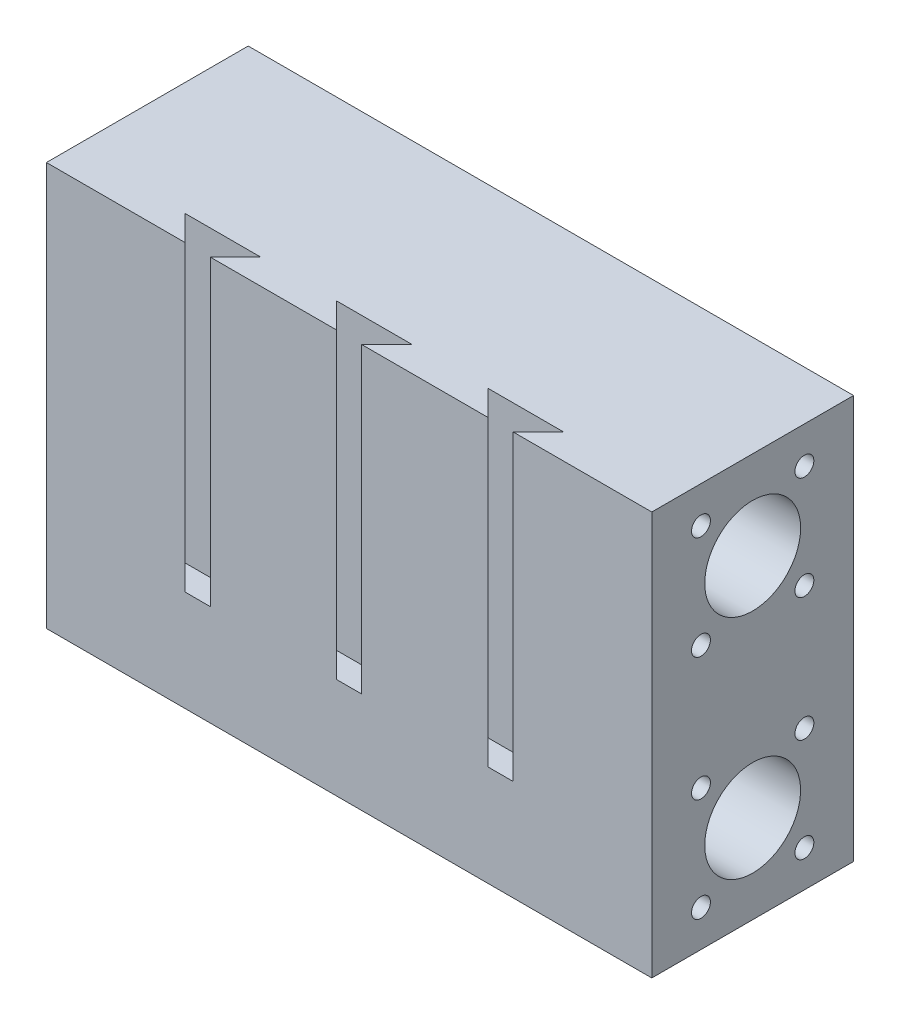
SolidWorks part; units mm, degrees
ref_plane "Front Plane" through (0, 0, 0) normal (0, 0, 1) x (1, 0, 0)
ref_plane "Top Plane" through (0, 0, 0) normal (0, 1, 0) x (1, 0, 0)
ref_plane "Right Plane" through (0, 0, 0) normal (1, 0, 0) x (0, 0, -1)
sketch "Sketch1" plane through (0, 0, 0) normal (0, 0, 1) x (1, 0, 0)
  line L1 (0, 0) -> (120, 0)
  line L2 (0, 0) -> (0, 80)
  line L3 (0, 80) -> (120, 80)
  line L4 (120, 0) -> (120, 80)
  dimension "D1" = 80
  dimension "D2" = 120
extrude "Boss-Extrude1" add sketch "Sketch1" along normal blind 40 contours L3 L4 L1 L2
sketch "Sketch2" plane through (0, 0, 0) normal (-1, 0, 0) x (0, 0, 1)
  line L0 (20, 80) -> (20, 0) construction
  line L1 (40, 80) -> (0, 80) construction
  line L2 (40, 0) -> (0, 0) construction
  line L3 (40, 40) -> (0, 40) construction
  line L4 (40, 0) -> (40, 80) construction
  line L5 (0, 0) -> (0, 80) construction
  line L6 (0, 62.5) -> (40, 62.5) construction
  line L7 (0, 17.5) -> (40, 17.5) construction
  circle A1 centre (30.25, 72.75) radius 1.85
  circle A2 centre (9.75, 72.75) radius 1.85
  circle A3 centre (30.25, 52.25) radius 1.85
  circle A4 centre (9.75, 52.25) radius 1.85
  circle A5 centre (9.75, 27.75) radius 1.85
  circle A6 centre (30.25, 27.75) radius 1.85
  circle A7 centre (30.25, 7.25) radius 1.85
  circle A9 centre (9.75, 7.25) radius 1.85
  dimension "D4" = 3.7
  dimension "D1" = 22.5
  dimension "D2" = 9.75
  dimension "D3" = 7.25
extrude "linear-bearing-screw-cuts" cut sketch "Sketch2" against normal blind 14
sketch "Sketch3" plane through (0, 0, 0) normal (-1, 0, 0) x (0, 0, 1)
  line L0 (20, 80) -> (20, 0) construction
  line L1 (40, 80) -> (0, 80) construction
  line L2 (40, 0) -> (0, 0) construction
  line L3 (0, 40) -> (40, 40) construction
  line L4 (0, 0) -> (0, 80) construction
  line L5 (40, 0) -> (40, 80) construction
  line L6 (0, 62.5) -> (40, 62.5) construction
  line L7 (0, 17.5) -> (40, 17.5) construction
  circle A0 centre (20, 62.5) radius 9.5
  circle A2 centre (20, 17.5) radius 9.5
  dimension "D2" = 19
  dimension "D1" = 45
extrude "linear-bearings-hole" cut sketch "Sketch3" against normal blind 55
sketch "Sketch4" plane through (120, 0, 0) normal (1, 0, 0) x (0, 0, -1)
  line L0 (-20, 80) -> (-20, 0) construction
  line L1 (-40, 80) -> (0, 80) construction
  line L2 (-40, 0) -> (0, 0) construction
  line L3 (-40, 40) -> (0, 40) construction
  line L4 (-40, 0) -> (-40, 80) construction
  line L5 (0, 0) -> (0, 80) construction
  line L6 (-40, 62.5) -> (0, 62.5) construction
  line L7 (-40, 17.5) -> (0, 17.5) construction
  circle A0 centre (-9.75, 72.75) radius 1.875
  circle A1 centre (-30.25, 72.75) radius 1.875
  circle A2 centre (-9.75, 52.25) radius 1.875
  circle A3 centre (-30.25, 52.25) radius 1.875
  circle A4 centre (-30.25, 27.75) radius 1.875
  circle A5 centre (-9.75, 27.75) radius 1.875
  circle A6 centre (-9.75, 7.25) radius 1.875
  circle A7 centre (-30.25, 7.25) radius 1.875
  dimension "D2" = 3.75
  dimension "D1" = 45
  dimension "D3" = 7.25
  dimension "D4" = 9.75
extrude "linear-bearing-screw-cuts2" cut sketch "Sketch4" against normal blind 14
sketch "Sketch5" plane through (120, 0, 0) normal (1, 0, 0) x (0, 0, -1)
  line L0 (-20, 80) -> (-20, 0) construction
  line L1 (-40, 80) -> (0, 80) construction
  line L2 (-40, 0) -> (0, 0) construction
  line L3 (0, 40) -> (-40, 40) construction
  line L4 (0, 0) -> (0, 80) construction
  line L5 (-40, 0) -> (-40, 80) construction
  line L6 (-40, 62.5) -> (0, 62.5) construction
  line L7 (-40, 17.5) -> (0, 17.5) construction
  circle A0 centre (-20, 62.5) radius 9.5
  circle A1 centre (-20, 17.5) radius 9.5
  dimension "D2" = 19
  dimension "D1" = 45
extrude "linear-bearings-hole2" cut sketch "Sketch5" against normal blind 55
sketch "Sketch10" plane through (0, 80, 0) normal (0, 1, 0) x (1, 0, 0)
  line L0 (60, 0) -> (60, -40) construction
  line L1 (0, 0) -> (120, 0) construction
  line L2 (0, -40) -> (120, -40) construction
  line L3 (75, 0) -> (75, -40) construction
  line L4 (92.5, -40) -> (97.5, -35)
  line L5 (97.5, -35) -> (82.5, -35)
  line L6 (82.5, -35) -> (87.5, -40)
  line L7 (87.5, -40) -> (92.5, -40)
  line L8 (120, -40) -> (120, 0) construction
  line L9 (67.5, -35) -> (62.5, -40)
  line L10 (52.5, -35) -> (67.5, -35)
  line L11 (57.5, -40) -> (52.5, -35)
  line L12 (62.5, -40) -> (57.5, -40)
  line L13 (37.5, -35) -> (32.5, -40)
  line L14 (22.5, -35) -> (37.5, -35)
  line L15 (27.5, -40) -> (22.5, -35)
  line L16 (32.5, -40) -> (27.5, -40)
  point P10 (90, -40)
  dimension "D1" = 45
  dimension "D2" = 15
  dimension "D3" = 5
  dimension "D4" = 30
  dimension "D5" = 45
extrude "Cut-Extrude7" cut sketch "Sketch10" against normal blind 60
